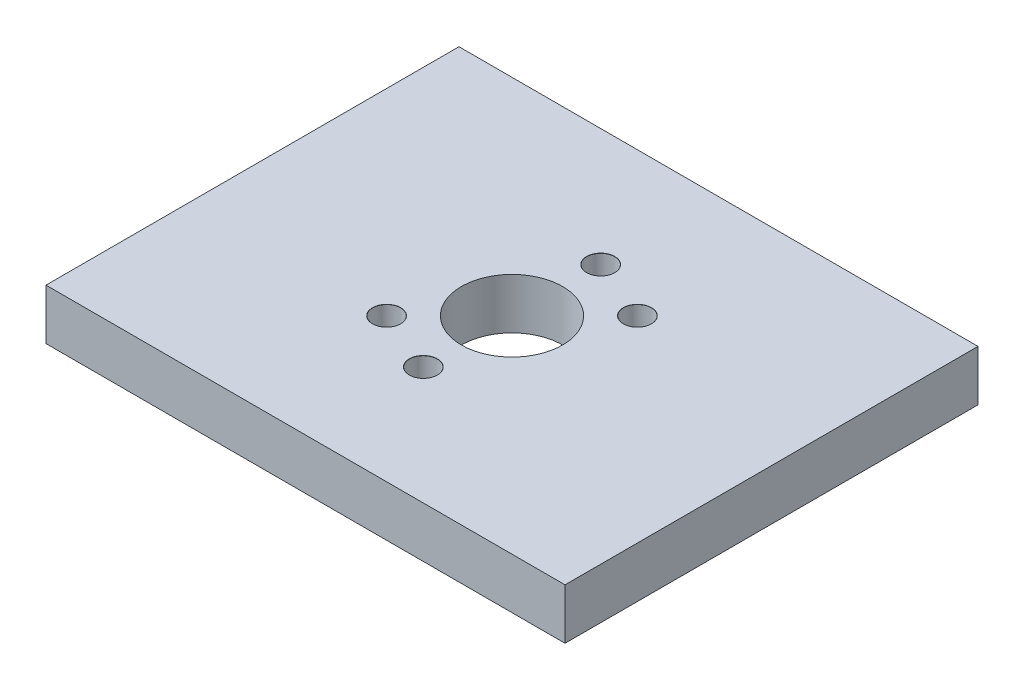
SolidWorks part; units mm, degrees
material "ABS PC"
ref_plane "Front Plane" through (0, 0, 0) normal (0, 0, 1) x (1, 0, 0)
ref_plane "Top Plane" through (0, 0, 0) normal (0, 1, 0) x (1, 0, 0)
ref_plane "Right Plane" through (0, 0, 0) normal (1, 0, 0) x (0, 0, -1)
sketch "Sketch1" plane through (0, 0, 0) normal (0, 1, 0) x (1, 0, 0)
  line L1 (-51.2219, -40.7542) -> (51.2219, -40.7542)
  line L2 (-51.2219, -40.7542) -> (-51.2219, 40.7542)
  line L3 (-51.2219, 40.7542) -> (51.2219, 40.7542)
  line L4 (51.2219, -40.7542) -> (51.2219, 40.7542)
  line L5 (-51.2219, -40.7542) -> (51.2219, 40.7542) construction
  line L6 (-51.2219, 40.7542) -> (51.2219, -40.7542) construction
  point P0 (0, 0)
extrude "Boss-Extrude1" add sketch "Sketch1" along normal blind 10
sketch "Sketch2" plane through (0, 10, 0) normal (0, 1, 0) x (1, 0, 0)
  circle A0 centre (0, 0) radius 17.5 construction
  circle A1 centre (0, 0) radius 17.5 construction
  circle A2 centre (0, 0) radius 17.5 construction
  circle A3 centre (0, 0) radius 17.5 construction
  circle A4 centre (0, 0) radius 17.5 construction
  circle A5 centre (0, 0) radius 17.5 construction
  circle A6 centre (0, 0) radius 17.5 construction
  circle A7 centre (0, 0) radius 17.5 construction
  point P3 (0, 17.5)
  point P5 (-17.5, 0)
  point P7 (12.3744, 12.3744)
  point P9 (17.5, 0)
  point P11 (12.3744, -12.3744)
  point P13 (0, -17.5)
  point P15 (-12.3744, -12.3744)
  point P16 (0, 0)
  point P18 (-12.3744, 12.3744)
  dimension "D1" = 35
  dimension "D2" = 8
hole_wizard "M5 Clearance Hole1" positions "Sketch3" profile "Sketch4" hole size "M5" standard "ANSI Metric" end condition through all
sketch "Sketch3" plane through (0, 10, 0) normal (0, 1, 0) x (1, 0, 0)
  point P0 (-12.3744, -12.3744)
  point P3 (0, -17.5)
  point P6 (12.3744, 12.3744)
  point P15 (0, 17.5)
sketch "Sketch4" plane through (-12.3744, 10, 12.3744) normal (1, 0, 0) x (0, 0, 1)
  line L0 (0, 0) -> (0, 10)
  line L1 (0, 10) -> (2.75, 10)
  line L2 (2.75, 10) -> (2.75, 0.025)
  line L3 (2.75, 0.025) -> (2.775, 0)
  line L5 (2.775, 0) -> (0, 0)
  line L6 (-2.75, 0.025) -> (-2.775, 0) construction
  line L11 (0, -6.35) -> (0, 107.95) construction
  dimension "Thru Hole Dia." = 5.5
  dimension "Thru Hole Depth" = 10
  dimension "Near C'Sink Dia." = 5.55
  dimension "Near C'Sink Angle" = 90
sketch "Sketch5" plane through (0, 10, 0) normal (0, 1, 0) x (1, 0, 0)
  circle A0 centre (0, 0) radius 10
  dimension "D1" = 20
extrude "Cut-Extrude1" cut sketch "Sketch5" against normal through all
